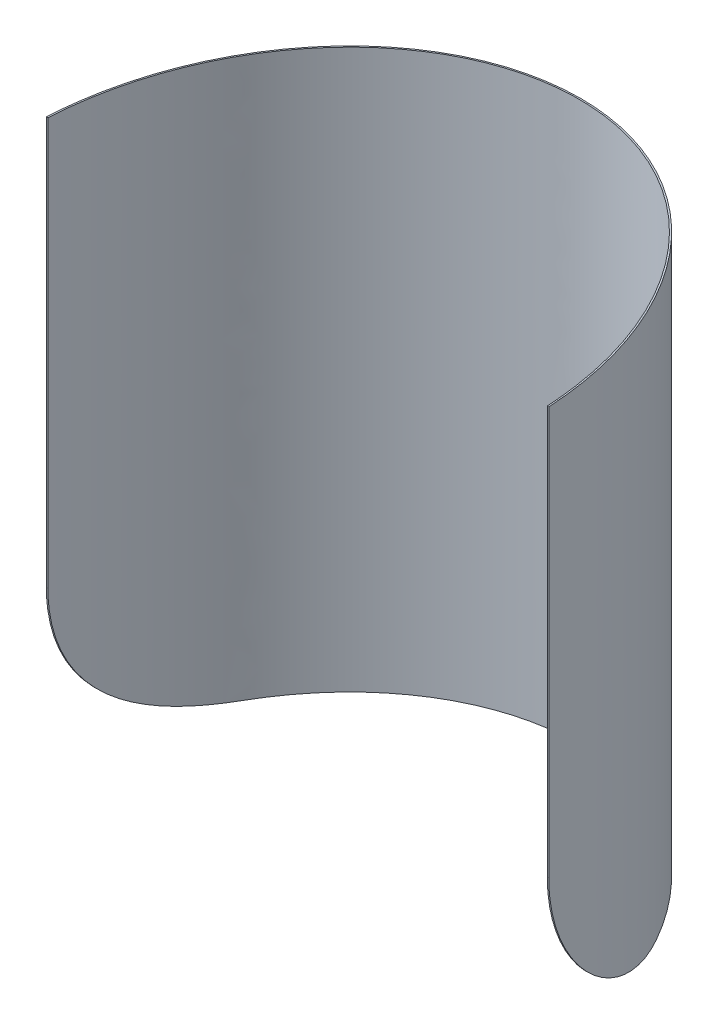
SolidWorks part; units mm, degrees
material "Perspex (TM) GS Acrylic Cast Sheet"
ref_plane "Front Plane" through (0, 0, 0) normal (0, 0, 1) x (1, 0, 0)
ref_plane "Top Plane" through (0, 0, 0) normal (0, 1, 0) x (1, 0, 0)
ref_plane "Right Plane" through (0, 0, 0) normal (1, 0, 0) x (0, 0, -1)
sketch "Sketch1" plane through (0, 0, 0) normal (0, 1, 0) x (1, 0, 0)
  line L0 (-83, 0) -> (83, 0) construction
  line L8 (-83, 0) -> (-83.5, 0)
  line L10 (83.5, 0) -> (83, 0)
  ellipse E0 centre (0, 0) end of major axis (0, -100) minor radius 83 (83, 0) -> (-83, 0) ccw
  spline S0 degree 1 poles (83.5, 0) (-83.5, 0) knots 0 0 1 1 construction
  spline S1 degree 3 poles (83.5, 0) (83.5, 6.5519) (82.4255, 19.7256) (77.6516, 38.6753) (69.8969, 56.1587) (59.4562, 71.487) (46.7261, 84.0734) (27.3511, 96.5596) (0, 103.127) (-27.3511, 96.5596) (-46.7261, 84.0734) (-59.4562, 71.487) (-69.8969, 56.1587) (-77.6516, 38.6753) (-82.4255, 19.7256) (-83.5, 6.5519) (-83.5, 0) knots 1.570796 1.570796 1.570796 1.570796 1.767146 1.963495 2.159845 2.356194 2.552544 2.748894 3.141593 3.534292 3.730641 3.926991 4.12334 4.31969 4.516039 4.712389 4.712389 4.712389 4.712389
  point P4 (0, 0)
  dimension "D2" = 100
  dimension "D3" = 166
  dimension "D5" = 0.5
extrude "Boss-Extrude1" add sketch "Sketch1" against normal blind 185.25
ref_plane "Plane1" [suppressed] through (-15.749, 0, -34.8802) normal (0.4115, 0, 0.9114) x (0.9114, 0, -0.4115)
sketch "Sketch3" [suppressed] plane through (-15.749, 0, -34.8802) normal (0.4115, 0, 0.9114) x (0.9114, 0, -0.4115)
  circle A0 centre (0, -17.25) radius 2.25
  point P2 (0, 0)
  dimension "D2" = 4.5
  dimension "D1" = 17.25
  dimension "D3" = 0
extrude "Cut-Extrude3" [suppressed] cut sketch "Sketch3" along normal up to surface (0.4997 mm away) from surface
ref_plane "Plane2" [suppressed] through (-15.6274, 0, 34.7726) normal (-0.4099, 0, 0.9121) x (0.9121, 0, 0.4099)
sketch "Sketch4" [suppressed] plane through (-15.6274, 0, 34.7726) normal (-0.4099, 0, 0.9121) x (0.9121, 0, 0.4099)
  circle A0 centre (0, -17.25) radius 2.25
  point P2 (0, 0)
  dimension "D1" = 4.5
  dimension "D2" = 0
  dimension "D3" = 17.25
extrude "Cut-Extrude4" [suppressed] cut sketch "Sketch4" against normal up to surface (0.4997 mm away) from surface
ref_plane "Plane3" [suppressed] through (-87.3262, 0, 22.2592) normal (-0.969, 0, 0.247) x (0.247, 0, 0.969)
sketch "Sketch5" [suppressed] plane through (-87.3262, 0, 22.2592) normal (-0.969, 0, 0.247) x (0.247, 0, 0.969)
  circle A0 centre (0, -17.25) radius 2.25
  point P0 (0, 0)
  dimension "D1" = 4.5
  dimension "D2" = 17.25
extrude "Cut-Extrude5" [suppressed] cut sketch "Sketch5" along normal up to surface (0.5006 mm away) from surface
ref_plane "Plane4" [suppressed] through (87.3262, 0, 22.2592) normal (0.969, 0, 0.247) x (0.247, 0, -0.969)
sketch "Sketch6" [suppressed] plane through (87.3262, 0, 22.2592) normal (0.969, 0, 0.247) x (0.247, 0, -0.969)
  circle A0 centre (0, -17.25) radius 2.25
  point P0 (0, 0)
  dimension "D1" = 4.5
  dimension "D2" = 17.25
extrude "Cut-Extrude6" [suppressed] cut sketch "Sketch6" along normal up to surface (0.5006 mm away) from surface
sketch "Sketch8" plane through (0, 0, 0) normal (0, 0, 1) x (1, 0, 0)
  line L0 (22.5, -17.5) -> (-22.5, -17.5) construction
  circle A0 centre (-22.5, -17.5) radius 4.25
  circle A1 centre (22.5, -17.5) radius 4.25
  point P0 (0, 0)
  point P5 (0, -17.5)
  dimension "D3" = 8.5
  dimension "D4" = 8.5
  dimension "D1" = 45
  dimension "D2" = 17.5
extrude "Cut-Extrude12" [suppressed] cut sketch "Sketch8" against normal up to surface (91.5042 mm away)
sketch "Sketch9" plane through (0, 0, 0) normal (0, 1, 0) x (1, 0, 0)
  line L1 (-100, 6.6) -> (100, 6.6)
  line L2 (-100, 6.6) -> (-100, 0)
  line L3 (-100, 0) -> (100, 0)
  line L4 (100, 6.6) -> (100, 0)
  dimension "D1" = 100
  dimension "D2" = 100
  dimension "D3" = 6.6
extrude "Cut-Extrude13" cut sketch "Sketch9" against normal up to surface (185.25 mm away) up to face at (20.875, -185.25, -25)
sketch "Sketch2" plane through (0, 0, 0) normal (1, 0, 0) x (0, 0, -1)
  line L2 (6.6, -185.25) -> (100.5, -185.25) construction
  line L3 (6.6, -185.25) -> (6.6, 0) construction
  line L7 (6.6, -185.25) -> (56.6, -185.25)
  line L10 (6.6, -135.25) -> (6.6, -185.25)
  arc A1 (6.6, -135.25) -> (56.6, -185.25) centre (56.6, -135.25) ccw
  dimension "D1" = 50
  dimension "D2" = 50
  dimension "D3" = 50
extrude "Cut-Extrude14" cut sketch "Sketch2" against normal up to surface and the other way up to surface up to face at (41.6595, -92.625, -6.6) other way up to face at (41.6595, -92.625, -6.6)
sketch "Sketch10" plane through (0, 0, 0) normal (0, 0, 1) x (1, 0, 0)
  line L1 (32, 0) -> (-32, 0)
  line L2 (32, 0) -> (32, -24)
  line L3 (32, -24) -> (-32, -24)
  line L4 (-32, 0) -> (-32, -24)
  line L5 (32, 0) -> (-32, -24) construction
  line L6 (32, -24) -> (-32, 0) construction
  dimension "D1" = 24
  dimension "D2" = 64
extrude "Cut-Extrude15" [suppressed] cut sketch "Sketch10" against normal blind 117
